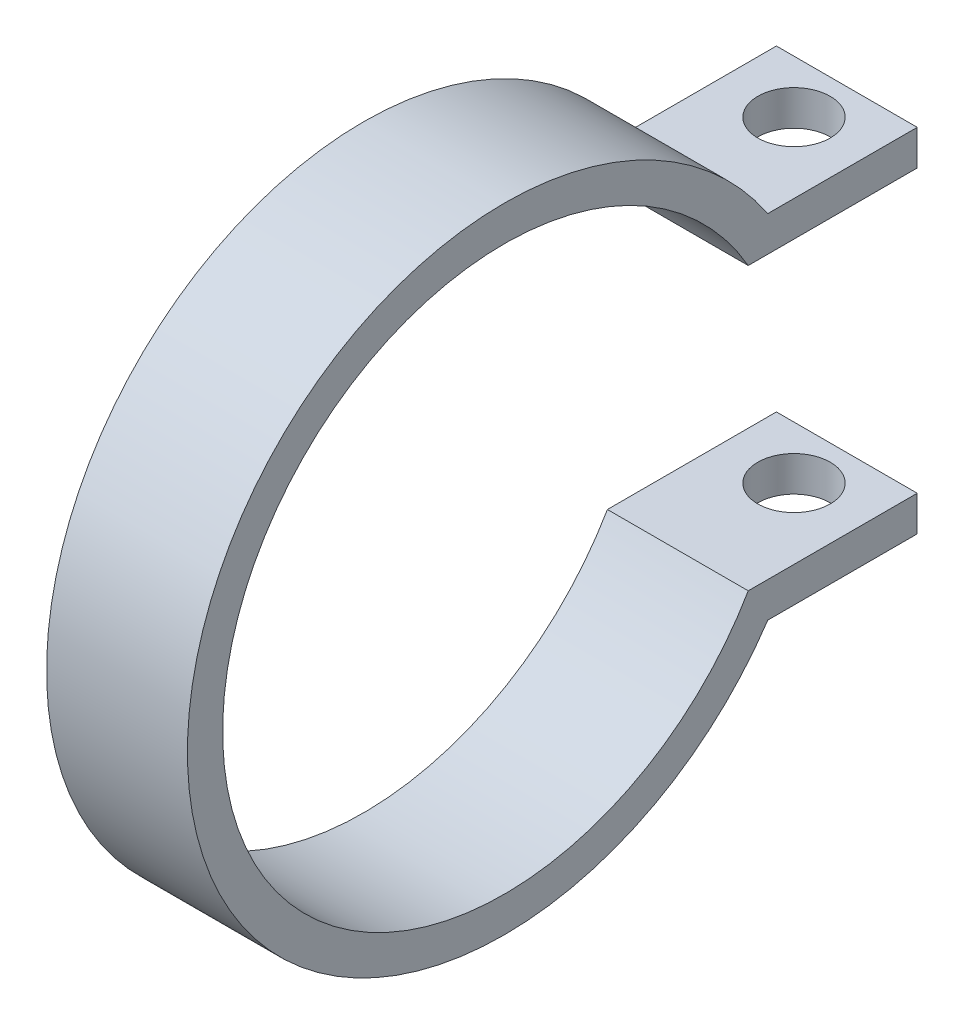
SolidWorks part; units mm, degrees
material "6061-T6 (SS)"
ref_plane "Front Plane" through (0, 0, 0) normal (1, 0, 0) x (0, 1, 0)
ref_plane "Top Plane" through (0, 0, 0) normal (0, 0, 1) x (0, 1, 0)
ref_plane "Right Plane" through (0, 0, 0) normal (0, 1, 0) x (-1, 0, 0)
sketch "Sketch2" plane through (0, 0, 0) normal (1, 0, 0) x (0, 1, 0)
  line L0 (-6.35, -10.9985) -> (6.35, -10.9985) construction
  line L1 (-6.35, -10.9985) -> (-6.35, -18.6185)
  line L2 (6.35, -10.9985) -> (6.35, -18.6185)
  line L3 (-7.9375, -11.8798) -> (-7.9375, -18.6185)
  line L4 (-7.9375, -18.6185) -> (-6.35, -18.6185)
  line L5 (6.35, -18.6185) -> (7.9375, -18.6185)
  line L6 (7.9375, -18.6185) -> (7.9375, -11.8798)
  arc A0 (6.35, -10.9985) -> (-6.35, -10.9985) centre (0, 0) ccw
  arc A1 (7.9375, -11.8798) -> (-7.9375, -11.8798) centre (0, 0) ccw
  dimension "D2" = 12.7
  dimension "D4" = 14.2875
  dimension "D1" = 12.7
  dimension "D3" = 7.62
  dimension "D5" = 1.5875
  dimension "D6" = 1.5875
extrude "Boss-Extrude1" add sketch "Sketch2" along normal blind 6.35
sketch "Sketch3" plane through (0, -7.9375, 0) normal (0, -1, 0) x (1, 0, 0)
  line L1 (3.175, -11.8798) -> (3.175, -18.6185) construction
  line L2 (6.35, -11.8798) -> (0, -11.8798) construction
  line L3 (6.35, -18.6185) -> (0, -18.6185) construction
  point P9 (3.175, -16.2373)
  dimension "D1" = 2.3813
hole_wizard "#4 Clearance Hole1" positions "Sketch3" profile "Sketch4" hole size "#4" standard "ANSI Inch" end condition through all
sketch "Sketch4" plane through (3.175, -7.9375, -16.2373) normal (1, 0, 0) x (0, 0, -1)
  line L0 (0, 0) -> (0, 22.225)
  line L1 (0, 22.225) -> (1.6319, 22.225)
  line L2 (1.6319, 22.225) -> (1.6319, 0)
  line L5 (1.6319, 0) -> (0, 0)
  line L11 (0, -6.35) -> (0, 107.95) construction
  dimension "Thru Hole Dia." = 3.2639
  dimension "Thru Hole Depth" = 22.225
